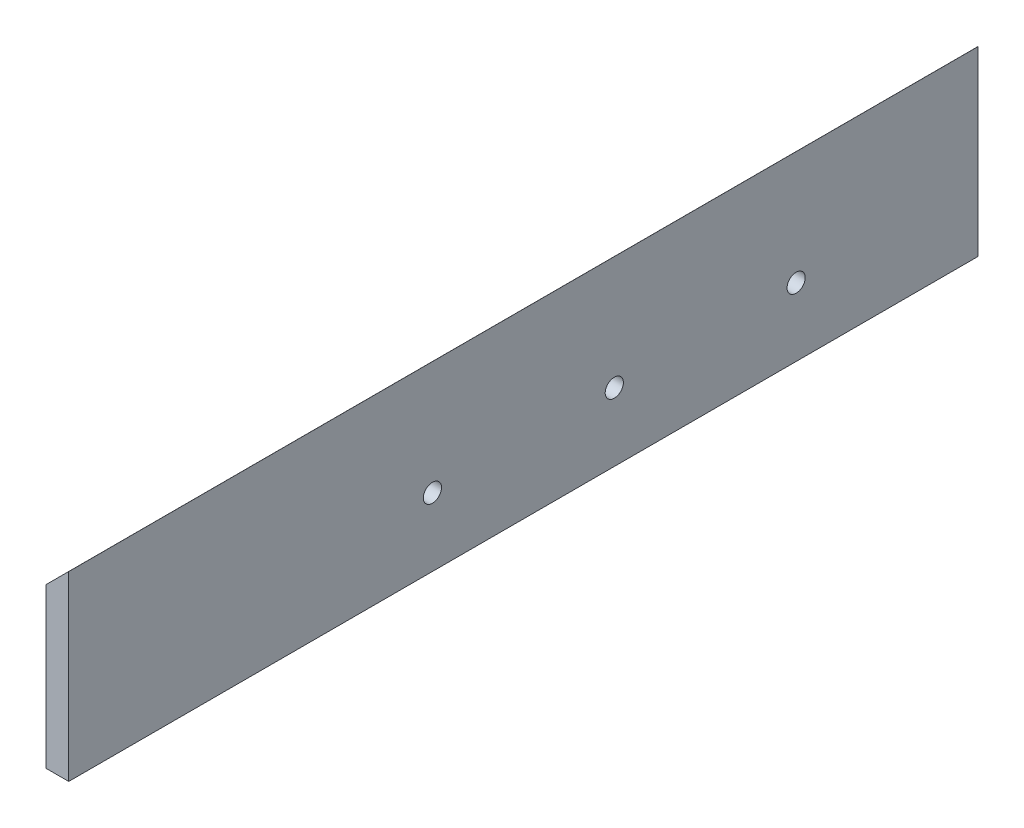
SolidWorks part; units mm, degrees
ref_plane "前基準面" through (0, 0, 0) normal (0, 0, 1) x (1, 0, 0)
ref_plane "上基準面" through (0, 0, 0) normal (0, 1, 0) x (1, 0, 0)
ref_plane "右基準面" through (0, 0, 0) normal (1, 0, 0) x (0, 0, -1)
sketch "草圖1" plane through (0, 0, 0) normal (0, 0, 1) x (1, 0, 0)
  line L0 (203.624, 1001.1769) -> (198.624, 1001.1769)
  line L1 (198.624, 1001.1769) -> (198.624, 1041.1769)
  line L7 (198.624, 1041.1769) -> (203.624, 1041.1629)
  line L8 (203.624, 1041.1629) -> (203.624, 1001.1769)
  dimension "D1" = 40
  dimension "D2" = 5
extrude "填料-伸長1" add sketch "草圖1" along normal blind 200
sketch "Sketch1" plane through (203.624, 0, 0) normal (1, 0, 0) x (0, 0, -1)
  line L0 (0, 1001.1769) -> (0, 1041.1629) construction
  line L1 (-200, 1001.1769) -> (0, 1001.1769) construction
  circle A0 centre (-40, 1016.1769) radius 2
  dimension "D1" = 4
  dimension "D2" = 40
  dimension "D3" = 15
chamfer "Chamfer1" distance 5 angle 45 1 edges at (198.624, 1041.1769, 100) first distance on face at (198.624, 1021.1769, 100)
extrude "Cut-Extrude1" cut sketch "Sketch1" against normal up to surface (5 mm away) up to face at (198.624, 1018.6769, 100)
pattern_linear "LPattern1" count 3 spacing 40 along (0, 0, 1) of "Cut-Extrude1"
